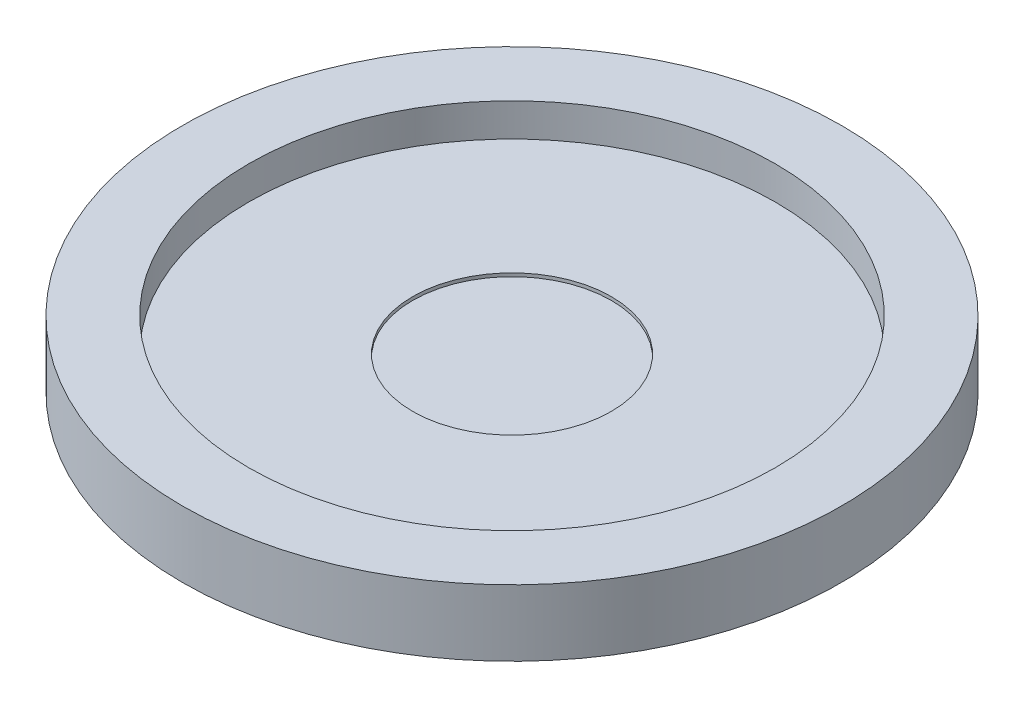
SolidWorks part; units mm, degrees
ref_plane "Front" through (0, 0, 0) normal (0, 0, 1) x (1, 0, 0)
ref_plane "Top" through (0, 0, 0) normal (0, 1, 0) x (1, 0, 0)
ref_plane "Right" through (0, 0, 0) normal (1, 0, 0) x (0, 0, -1)
sketch "Sketch1" plane through (0, 0, 0) normal (0, 1, 0) x (1, 0, 0)
  circle A0 centre (0, 0) radius 9945.75
  dimension "D1" = 19891.5
extrude "Boss-Extrude1" add sketch "Sketch1" along normal blind 2000
sketch "Sketch2" plane through (0, 2000, 0) normal (0, 1, 0) x (1, 0, 0)
  circle A0 centre (0, 0) radius 7945.75
  circle A1 centre (0, 0) radius 9945.75 construction
  dimension "D1" = 2000
extrude "Cut-Extrude1" cut sketch "Sketch2" against normal blind 1000
sketch "Sketch3" plane through (0, 1000, 0) normal (0, 1, 0) x (1, 0, 0)
  circle A0 centre (0, 0) radius 3000
  dimension "D1" = 6000
extrude "Cut-Extrude2" cut sketch "Sketch3" against normal blind 100
equation "\"Radius\"= 12"
equation "\"diameter\"=19.8915"
equation "\"D1@Sketch1\"=\"diameter\""
equation "\"height\"= 2"
equation "\"D1@Boss-Extrude1\"=\"height\""
equation "\"pit\"=2"
equation "\"D1@Sketch2\"=\"pit\""
equation "\"basehole\"=6"
equation "\"D1@Sketch3\"=\"basehole\""
